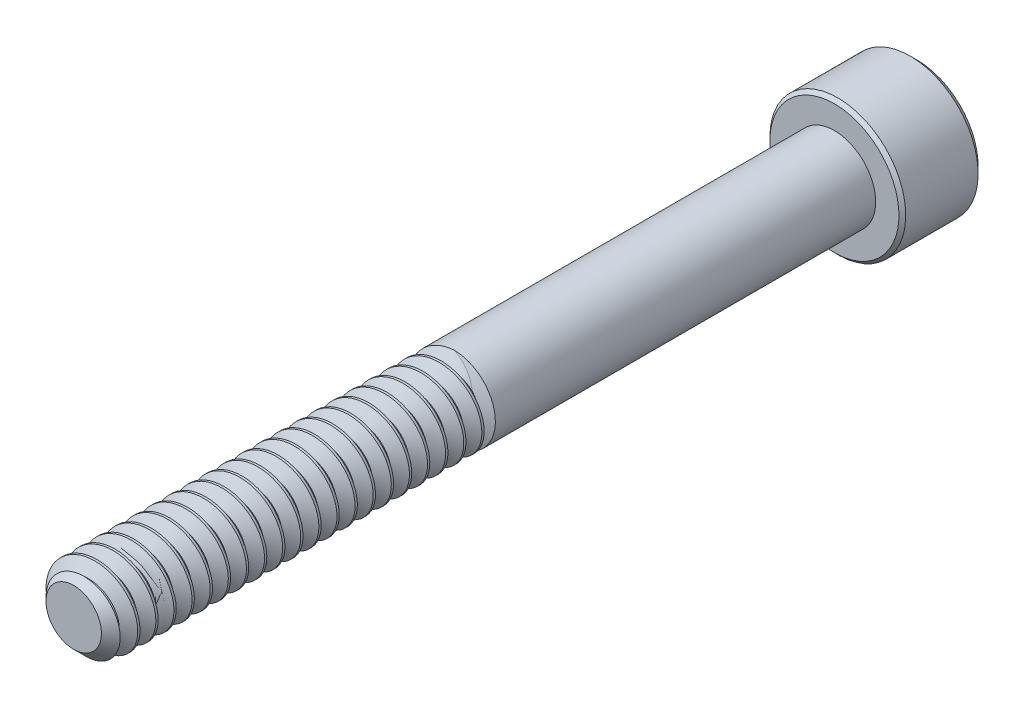
SolidWorks part; units mm, degrees
material "AISI 304"
ref_plane "Front Plane" through (0, 0, 0) normal (0, 0, 1) x (1, 0, 0)
ref_plane "Top Plane" through (0, 0, 0) normal (0, 1, 0) x (1, 0, 0)
ref_plane "Right Plane" through (0, 0, 0) normal (1, 0, 0) x (0, 0, -1)
sketch "Sketch0" plane through (0, 0, 0) normal (1, 0, 0) x (0, 0, -1)
  line L0 (0, 0) -> (44.45, 0) construction
  point P2 (49.276, 0)
  point P4 (22.225, 0)
  dimension "D1" = 44.45
  dimension "D2" = 4.826
  dimension "Min Thread" = 22.225
sketch "Sketch1" plane through (0, 0, 0) normal (0, 0, 1) x (1, 0, 0)
  circle A0 centre (0, 0) radius 2.413
  dimension "OD" = 4.826
extrude "Extrude1" add sketch "Sketch1" against normal blind 44.45
sketch "Sketch2" plane through (0, 0, 0) normal (0, 0, 1) x (1, 0, 0)
  circle A0 centre (0, 0) radius 2.413 construction
  circle A1 centre (0, 0) radius 2.413
curve "Helix/Spiral1" pitch 1.0583 height 45.5083 turns 43 parameters "pitch"=1.0583
chamfer "Chamfer3" distance 0.7937 angle 45 1 edges at (2.413, 0, 0)
sketch "Sketch3" plane through (0, 0, 0) normal (1, 0, 0) x (0, 0, -1)
  line L0 (-0.926, 2.413) -> (-0.5292, 1.7256)
  line L1 (-0.5292, 1.7256) -> (-0.3969, 1.7256)
  line L2 (-0.3969, 1.7256) -> (0, 2.413)
  line L3 (-0.926, 2.413) -> (0, 2.413)
  line L4 (-0.463, 2.413) -> (-0.463, 1.7256) construction
  line L5 (-0.7276, 2.0693) -> (-0.1984, 2.0693) construction
  line L6 (0, 2.413) -> (0, -2.413) construction
  dimension "D1" = 0.1323
  dimension "D2" = 0.5292
  dimension "D3" = 60
sweep "Cut-Sweep1" cut profiles "Sketch3" path "Helix/Spiral1"
sketch "Sketch5" plane through (0, 0, 0) normal (1, 0, 0) x (0, 0, -1)
  line L0 (44.45, -1.7471) -> (44.45, 1.7217) construction
  line L1 (44.45, 2.413) -> (22.225, 2.413)
  line L2 (44.45, 2.413) -> (44.45, 0)
  line L3 (44.45, 0) -> (21.3467, 0)
  line L4 (0, 0) -> (44.45, 0) construction
  line L5 (22.225, 2.413) -> (21.3467, 0)
  line L6 (0, 0) -> (46.99, 0) construction
  dimension "D1" = 70
  dimension "D3" = 2.54
revolve "partially thread" add sketch "Sketch5" angle 360 about L6
sketch "Sketch6" plane through (0, 0, -44.45) normal (0, 0, -1) x (-1, 0, 0)
  circle A0 centre (0, 0) radius 3.9688
  dimension "head dia" = 7.9375
extrude "Extrude2" add sketch "Sketch6" along normal blind 4.826
sketch "Sketch7" plane through (0, 0, -49.276) normal (0, 0, -1) x (-1, 0, 0)
  line L1 (0, 2.2914) -> (-1.9844, 1.1457)
  line L2 (-1.9844, 1.1457) -> (-1.9844, -1.1457)
  line L3 (-1.9844, -1.1457) -> (0, -2.2914)
  line L4 (0, -2.2914) -> (1.9844, -1.1457)
  line L5 (1.9844, -1.1457) -> (1.9844, 1.1457)
  line L6 (1.9844, 1.1457) -> (0, 2.2914)
  circle A0 centre (0, 0) radius 1.9844 construction
  dimension "hex dia" = 3.9688
extrude "Cut-Extrude1" cut sketch "Sketch7" against normal blind 2.9766
sketch "Sketch8" plane through (0, 0, -49.276) normal (0, 0, -1) x (-1, 0, 0)
  circle A0 centre (0, 0) radius 2.2914
extrude "Cut-Extrude2" cut sketch "Sketch8" against normal through all draft 45
chamfer "Chamfer1" distance 0.3969 angle 45 1 edges at (-3.9688, 0, -49.276)
chamfer "Chamfer2" distance 0.1984 angle 45 1 edges at (-3.9688, 0, -44.45)
sketch "Sketch9" plane through (0, 0, 0) normal (1, 0, 0) x (0, 0, -1)
  line L0 (0, 2.413) -> (0, -2.413) construction
  line L1 (2.6458, 2.413) -> (2.6458, -2.413) construction
  line L2 (49.276, 3.9688) -> (49.276, -3.9688) construction
  line L3 (44.45, 3.9688) -> (44.45, -3.9688) construction
  line L4 (44.45, 3.7703) -> (44.45, -3.7703) construction
  line L5 (49.276, -3.5719) -> (49.276, 3.5719) construction
  line L6 (44.45, -3.9688) -> (44.45, 3.9688) construction
  line L7 (0, 1.6193) -> (0, -1.6193) construction
  line L8 (-0.926, 2.413) -> (0, 2.413) construction
  line L9 (2.6458, 0) -> (0, 0) construction
  dimension "D1" = 2.6458
equation "\"D3@Helix/Spiral1\" = \"screw length@Extrude1\"+\"pitch@Helix/Spiral1\""
equation "\"D1@Sketch3\" = \"pitch@Helix/Spiral1\"*.125"
equation "\"D2@Sketch3\" = \"pitch@Helix/Spiral1\"*.5"
equation "\"D1@Cut-Extrude1\" = \"hex dia@Sketch7\"*.75"
equation "\"D1@Chamfer1\" = \"head dia@Sketch6\"*.05"
equation "\"D1@Sketch9\" = \"pitch@Helix/Spiral1\"*2.50"
equation "\"D1@Chamfer2\" = \"D1@Chamfer1\"/2"
equation "\"D1@Chamfer3\" = \"pitch@Helix/Spiral1\"*.750"
equation "\"D1@Sketch0\" = \"screw length@Extrude1\""
equation "\"D2@Sketch0\" = \"head depth@Extrude2\""
